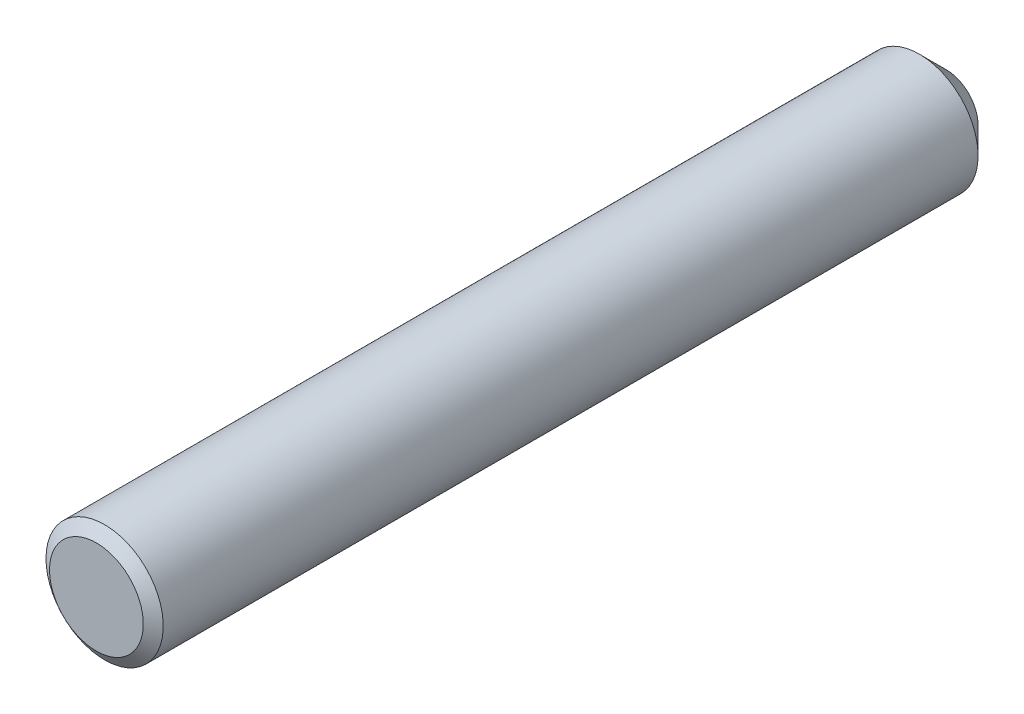
SolidWorks part; units mm, degrees
ref_plane "Front" through (0, 0, 0) normal (0, 0, 1) x (1, 0, 0)
ref_plane "Top" through (0, 0, 0) normal (0, 1, 0) x (1, 0, 0)
ref_plane "Right" through (0, 0, 0) normal (1, 0, 0) x (0, 0, -1)
sketch "Sketch22" plane through (0, 0, 0) normal (1, 0, 0) x (0, 0, -1)
  line L0 (-12.7, 0) -> (-12.7, 1.4021)
  line L1 (-12.7, 1.4021) -> (-12.4546, 1.7526)
  line L2 (-12.4546, 1.7526) -> (11.9062, 1.7526)
  line L3 (11.9062, 1.7526) -> (12.7, 0.9588)
  line L4 (-0.2742, 1.7526) -> (-0.2742, -1.7526) construction
  line L5 (12.7, 0) -> (-12.7, 0)
  line L7 (12.7, 0) -> (12.7, 0.9588)
  line L10 (-12.7, 1.4021) -> (-12.7, -1.4021) construction
  point P13 (-0.2742, 0)
  dimension "Length" = 25.4
  dimension "D3" = 35
  dimension "D1" = 2.8042
  dimension "Dia" = 3.5052
  dimension "D2" = 0.7937
  dimension "D4" = 45
revolve "Revolve1" add sketch "Sketch22" angle 360 about L5
ref_plane "Plane1" through (0, 0, -12.7) normal (0, 0, 1) x (1, 0, 0)
sketch "Sketch27" [suppressed] plane through (0, 0, -12.7) normal (0, 0, 1) x (1, 0, 0)
  circle A0 centre (0, 0) radius 1.7526 construction
  circle A1 centre (0, 0) radius 1.7526
curve "Helix/Spiral1" [suppressed] pitch 0.7937 height 26.1937 turns 33
sketch "Sketch28" plane through (0, 0, 0) normal (1, 0, 0) x (0, 0, -1)
  line L0 (12.7, 1.7526) -> (13.3945, 1.7526)
  line L1 (13.3945, 1.7526) -> (13.0969, 1.237)
  line L2 (13.0969, 1.237) -> (12.9977, 1.237)
  line L3 (12.9977, 1.237) -> (12.7, 1.7526)
  line L4 (12.8488, 1.4948) -> (13.2457, 1.4948) construction
  line L6 (-12.4546, 1.7526) -> (11.9062, 1.7526) construction
  line L7 (12.7, 1.9279) -> (12.7, -1.9279) construction
  dimension "D1" = 0.0992
  dimension "D3" = 60
  dimension "D2" = 0.3969
sweep "Cut-Sweep2" [suppressed] cut profiles "Sketch28" path "Helix/Spiral1"
sketch "Sketch23" [suppressed] plane through (0, 0, 12.7) normal (0, 0, 1) x (1, 0, 0)
  line L1 (0, 0.9165) -> (-0.7937, 0.4583)
  line L2 (-0.7937, 0.4583) -> (-0.7937, -0.4583)
  line L3 (-0.7937, -0.4583) -> (0, -0.9165)
  line L4 (0, -0.9165) -> (0.7937, -0.4583)
  line L5 (0.7937, -0.4583) -> (0.7937, 0.4583)
  line L6 (0.7937, 0.4583) -> (0, 0.9165)
  circle A0 centre (0, 0) radius 0.7937 construction
  dimension "Hex" = 1.5875
extrude "Cut-Extrude10" [suppressed] cut sketch "Sketch23" against normal blind 0.9922
sketch "Sketch24" [suppressed] plane through (0, 0, 12.7) normal (0, 0, 1) x (1, 0, 0)
  circle A0 centre (0, 0) radius 0.9165
extrude "Cut-Extrude11" [suppressed] cut sketch "Sketch24" against normal through all draft 45
sketch "Sketch26" [suppressed] plane through (0, 0, 11.7078) normal (0, 0, 1) x (1, 0, 0)
  circle A0 centre (0, 0) radius 0.7937 construction
  circle A1 centre (0, 0) radius 0.7937
extrude "Cut-Extrude12" [suppressed] cut sketch "Sketch26" against normal through all draft 60
sketch "Sketch30" plane through (0, 0, 0) normal (1, 0, 0) x (0, 0, -1)
  line L0 (-12.4546, 1.7526) -> (11.9062, 1.7526) construction
  line L1 (-12.7, 0) -> (-12.7, 1.4021) construction
  line L2 (12.7, 0) -> (12.7, 0.9588) construction
  point P0 (-12.7, 1.7526)
  point P1 (12.7, 1.7526)
  point P2 (12.7, -1.7526)
  point P11 (10.7156, -1.7526)
  dimension "D1" = 1.9844
equation "\"D1@Sketch28\" = \"D4@Helix/Spiral1\" * .125"
equation "\"D3@Helix/Spiral1\" = \"Length@Sketch22\" + \"D4@Helix/Spiral1\""
equation "\"D1@Sketch30\" = \"D4@Helix/Spiral1\" * 2.5"
equation "\"hex Depth@Cut-Extrude10\" = \"Hex@Sketch23\" * .625"
equation "\"D2@Sketch28\" = \"D4@Helix/Spiral1\" * .5"
equation "\"D1@Sketch22\" = \"Dia@Sketch22\" * .8"
equation "\"D2@Sketch22\" = \"D4@Helix/Spiral1\""
